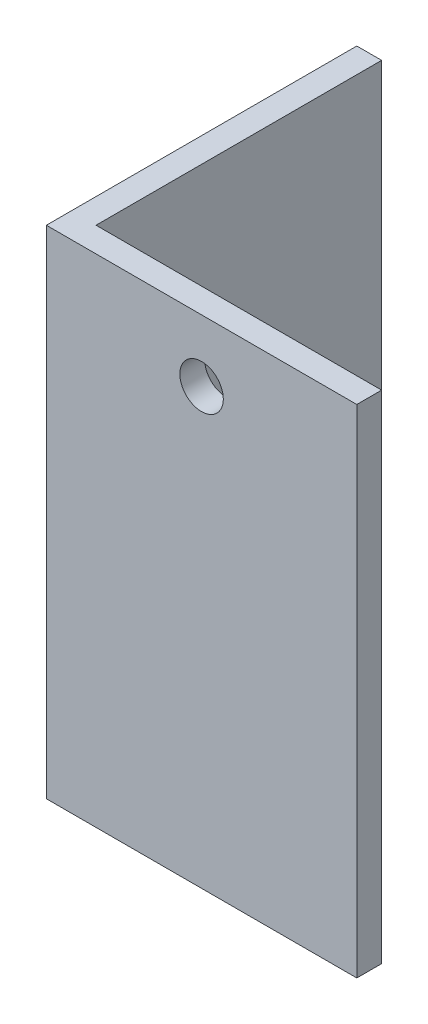
SolidWorks part; units mm, degrees
ref_plane "Front Plane" through (0, 0, 0) normal (0, 0, 1) x (1, 0, 0)
ref_plane "Top Plane" through (0, 0, 0) normal (0, 1, 0) x (1, 0, 0)
ref_plane "Right Plane" through (0, 0, 0) normal (1, 0, 0) x (0, 0, -1)
sketch "Sketch1" plane through (0, 0, 0) normal (0, 1, 0) x (1, 0, 0)
  line L1 (0, 0) -> (25, 0)
  line L2 (0, 0) -> (0, 25)
  line L3 (0, 25) -> (2, 25)
  line L4 (25, 0) -> (25, 2)
  line L7 (25, 2) -> (2, 2)
  line L8 (2, 25) -> (2, 2)
  dimension "D1" = 25
  dimension "D2" = 25
  dimension "D3" = 2
  dimension "D4" = 2
extrude "Boss-Extrude1" add sketch "Sketch1" along normal blind 40
sketch "Sketch2" plane through (0, 0, 0) normal (1, 0, 0) x (0, 0, -1)
  line L3 (0, 40) -> (0, 0) construction
  line L4 (25, 0) -> (0, 0) construction
  circle A1 centre (10, 5) radius 1.75
  dimension "D1" = 3.5
  dimension "D2" = 10
  dimension "D3" = 5
extrude "Cut-Extrude1" cut sketch "Sketch2" along normal blind 50
sketch "Sketch3" plane through (0, 0, 0) normal (0, 0, -1) x (-1, 0, 0)
  line L3 (0, 40) -> (0, 0) construction
  line L4 (0, 0) -> (-25, 0) construction
  circle A0 centre (-12.5, 35) radius 1.75
  point P2 (-11.049, 35)
  point P3 (0, 0)
  dimension "D1" = 12.5
  dimension "D2" = 3.5
  dimension "D3" = 35
extrude "Cut-Extrude2" cut sketch "Sketch3" along normal blind 50
